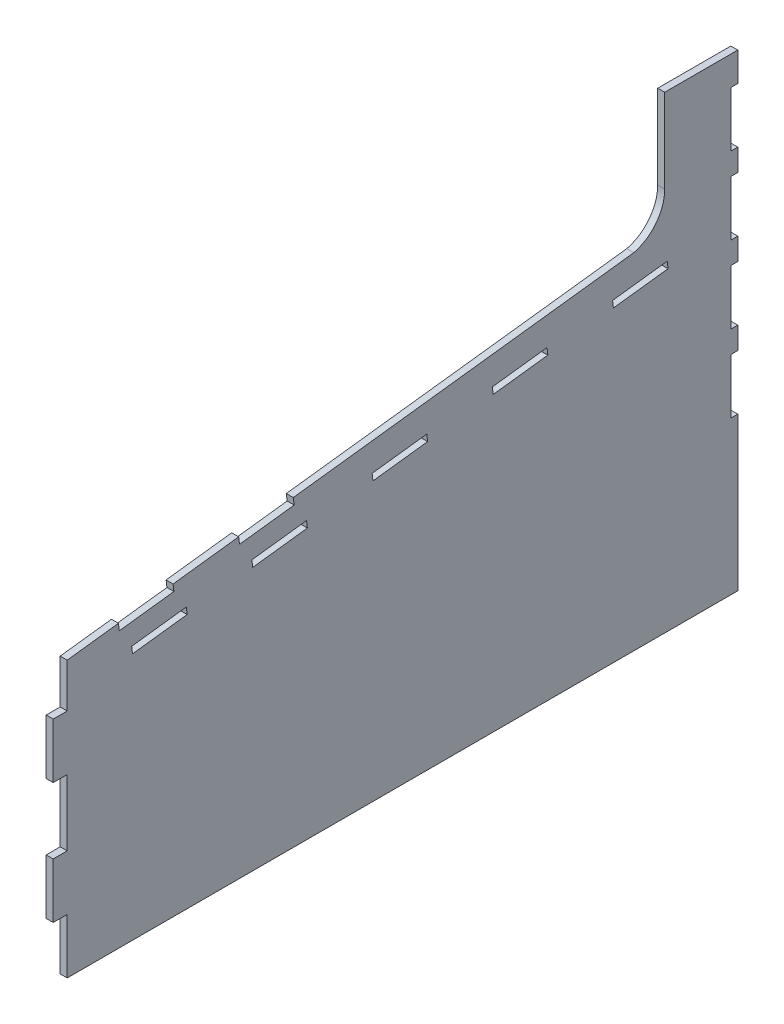
SolidWorks part; units mm, degrees
material "Beech"
ref_plane "Front Plane" through (0, 0, 0) normal (0, 0, 1) x (1, 0, 0)
ref_plane "Top Plane" through (0, 0, 0) normal (0, 1, 0) x (1, 0, 0)
ref_plane "Right Plane" through (0, 0, 0) normal (1, 0, 0) x (0, 0, -1)
sketch "Sketch1" plane through (0, 0, 0) normal (1, 0, 0) x (0, 0, -1)
  line L1 (0, 0) -> (609, 0)
  line L2 (0, 0) -> (0, 50)
  line L4 (609, 0) -> (609, 138.97)
  line L6 (609, 258.97) -> (609, 278.97)
  line L7 (609, 425.32) -> (542.65, 425.32)
  line L8 (542.65, 349.09) -> (542.65, 425.32)
  line L9 (0, 250) -> (609, 250) construction
  line L10 (514.5695, 313.1812) -> (609, 324.7758) construction
  line L11 (-12.7, 160) -> (-12.7, 210)
  line L12 (0, 50) -> (-12.7, 50)
  line L14 (0, 100) -> (-12.7, 100)
  line L15 (-12.7, 50) -> (-12.7, 100)
  line L16 (0, 160) -> (-12.7, 160)
  line L18 (0, 210) -> (-12.7, 210)
  line L19 (0, 210) -> (0, 250)
  line L21 (0, 100) -> (0, 160)
  line L33 (0, 250) -> (514.5695, 313.1812) construction
  line L34 (0, 250) -> (514.5695, 313.1812)
  line L36 (609, 398.97) -> (602.65, 398.97)
  line L38 (609, 348.97) -> (602.65, 348.97)
  line L39 (602.65, 398.97) -> (602.65, 348.97)
  line L40 (609, 328.97) -> (602.65, 328.97)
  line L41 (602.65, 328.97) -> (602.65, 278.97)
  line L42 (609, 278.97) -> (602.65, 278.97)
  line L44 (609, 258.97) -> (602.65, 258.97)
  line L45 (602.65, 258.97) -> (602.65, 208.97)
  line L46 (609, 208.97) -> (602.65, 208.97)
  line L48 (609, 188.97) -> (602.65, 188.97)
  line L49 (602.65, 188.97) -> (602.65, 138.97)
  line L50 (609, 138.97) -> (602.65, 138.97)
  line L51 (609, 188.97) -> (609, 208.97)
  line L54 (609, 328.97) -> (609, 348.97)
  line L56 (609, 398.97) -> (609, 425.32)
  arc A0 (514.5695, 313.1812) -> (542.65, 349.09) centre (505.65, 349.09) ccw
  dimension "D4" = 37
  dimension "D1" = 609
  dimension "D2" = 250
  dimension "D3" = 66.35
  dimension "D5" = 7
  dimension "D6" = 175.32
  dimension "D7" = 76.23
  dimension "D8" = 12.7
  dimension "D9" = 50
  dimension "D10" = 50
  dimension "D11" = 2
  dimension "D12" = 40
  dimension "D13" = 6.35
  dimension "D14" = 50
  dimension "D15" = 26.35
  dimension "D17" = 138.97
  dimension "D16" = 4
extrude "Boss-Extrude1" add sketch "Sketch1" along normal blind 6.35
sketch "Sketch2" plane through (6.35, 0, 0) normal (1, 0, 0) x (0, 0, -1)
  line L0 (514.5695, 313.1812) -> (609, 324.7758) construction
  line L1 (609, 0) -> (609, 138.97) construction
  line L2 (205.3392, 275.2125) -> (155.7119, 269.119)
  line L3 (0, 224.4093) -> (609, 299.185) construction
  line L4 (0, 50) -> (0, 0) construction
  line L5 (58.5602, 231.5995) -> (59.3341, 225.2969)
  line L6 (59.3341, 225.2969) -> (108.9614, 231.3903)
  line L7 (108.9614, 231.3903) -> (108.1875, 237.693)
  line L8 (108.1875, 237.693) -> (58.5602, 231.5995)
  line L9 (217.3676, 251.0986) -> (167.7403, 245.0052)
  line L10 (167.7403, 245.0052) -> (168.5142, 238.7025)
  line L11 (168.5142, 238.7025) -> (218.1415, 244.796)
  line L12 (218.1415, 244.796) -> (217.3676, 251.0986)
  line L13 (326.5477, 264.5043) -> (276.9204, 258.4108)
  line L14 (276.9204, 258.4108) -> (277.6942, 252.1081)
  line L15 (277.6942, 252.1081) -> (327.3216, 258.2016)
  line L16 (327.3216, 258.2016) -> (326.5477, 264.5043)
  line L17 (435.7278, 277.9099) -> (386.1005, 271.8164)
  line L18 (386.1005, 271.8164) -> (386.8743, 265.5138)
  line L19 (386.8743, 265.5138) -> (436.5016, 271.6072)
  line L20 (436.5016, 271.6072) -> (435.7278, 277.9099)
  line L21 (544.9078, 291.3155) -> (495.2805, 285.2221)
  line L22 (495.2805, 285.2221) -> (496.0544, 278.9194)
  line L23 (496.0544, 278.9194) -> (545.6817, 285.0129)
  line L24 (545.6817, 285.0129) -> (544.9078, 291.3155)
  line L25 (155.7119, 269.119) -> (156.4858, 262.8163)
  line L26 (514.5695, 313.1812) -> (0, 250) construction
  line L27 (0, 224.4093) -> (-3.0955, 249.6199) construction
  line L28 (-3.0955, 249.6199) -> (0, 250) construction
  line L29 (46.5318, 255.7134) -> (47.3057, 249.4107)
  line L30 (47.3057, 249.4107) -> (96.933, 255.5042)
  line L31 (96.933, 255.5042) -> (96.1591, 261.8069)
  line L32 (96.1591, 261.8069) -> (46.5318, 255.7134)
  line L33 (156.4858, 262.8163) -> (206.1131, 268.9098)
  line L34 (206.1131, 268.9098) -> (205.3392, 275.2125)
  dimension "D1" = 25.4
  dimension "D2" = 50
  dimension "D3" = 6.35
  dimension "D4" = 59
  dimension "D5" = 90
  dimension "D6" = 6.35
  dimension "D7" = 50
  dimension "D8" = 50
  dimension "D9" = 2
extrude "Cut-Extrude1" cut sketch "Sketch2" against normal blind 6.35
